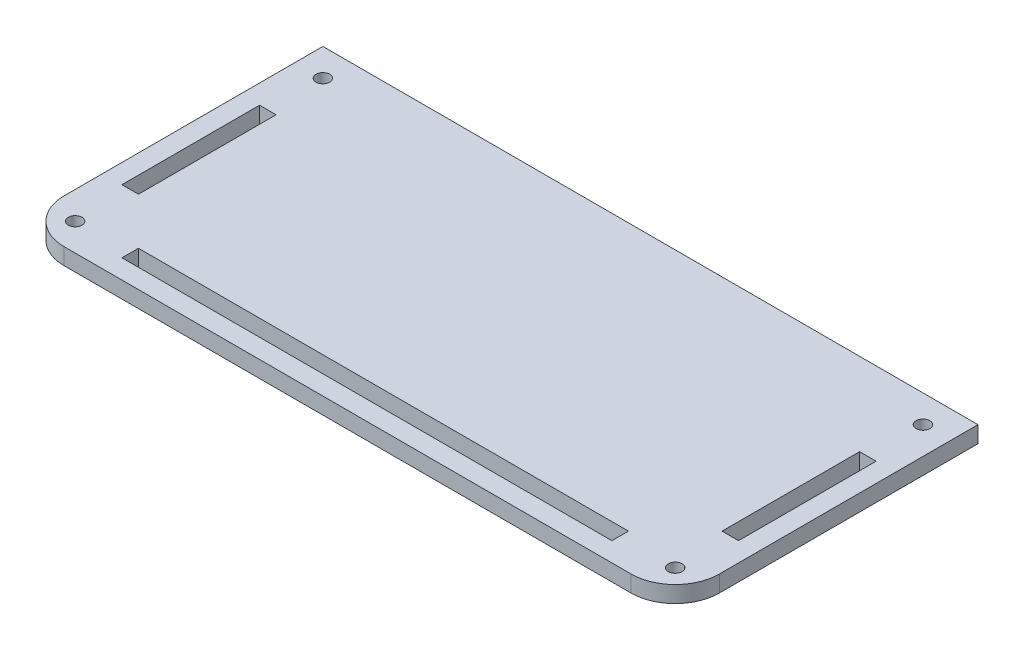
SolidWorks part; units mm, degrees
material "PVC rigido"
ref_plane "Piano frontale" through (0, 0, 0) normal (0, 0, 1) x (1, 0, 0)
ref_plane "Piano superiore" through (0, 0, 0) normal (0, 1, 0) x (1, 0, 0)
ref_plane "Piano destro" through (0, 0, 0) normal (1, 0, 0) x (0, 0, -1)
sketch "Schizzo1" plane through (0, 0, 0) normal (0, 1, 0) x (1, 0, 0)
  line L1 (-59.5, -27.5) -> (59.5, -27.5)
  line L2 (-59.5, -27.5) -> (-59.5, 27.5)
  line L3 (-59.5, 27.5) -> (59.5, 27.5)
  line L4 (59.5, -27.5) -> (59.5, 27.5)
  line L5 (-59.5, -27.5) -> (59.5, 27.5) construction
  line L6 (-59.5, 27.5) -> (59.5, -27.5) construction
  line L7 (67.5, 0) -> (59.5, 0) construction
  line L8 (67.5, -27.5) -> (67.5, 21.5) construction
  line L9 (-59.5, 0) -> (-67.5, 0) construction
  line L10 (-67.5, 21.5) -> (-67.5, -27.5) construction
  point P0 (0, 0)
  dimension "D1" = 8
  dimension "D2" = 55
extrude "Estrusione-Estrusione1" add sketch "Schizzo1" along normal blind 3
hole_wizard "Foro filettato M3x0.5-1" positions "Schizzo3" profile "Schizzo2" tap size "M3x0.5" standard "Ansi Metric" end condition through all
sketch "Schizzo3" plane through (0, 3, 0) normal (0, 1, 0) x (1, 0, 0)
  line L16 (54.5, -22.5) -> (54.5, 22.5)
  line L17 (54.5, 22.5) -> (-54.5, 22.5)
  line L18 (-54.5, 22.5) -> (-54.5, -22.5)
  line L19 (-54.5, -22.5) -> (54.5, -22.5)
  line L20 (54.5, -22.5) -> (54.5, 22.5) construction
  line L21 (54.5, 22.5) -> (-54.5, 22.5) construction
  line L22 (-54.5, 22.5) -> (-54.5, -22.5) construction
  line L23 (-54.5, -22.5) -> (54.5, -22.5) construction
  point P0 (-54.5, -22.5)
  point P2 (54.5, -22.5)
  point P4 (54.5, 22.5)
  point P6 (-54.5, 22.5)
  dimension "D1" = 5
sketch "Schizzo2" plane through (-54.5, 3, 22.5) normal (1, 0, 0) x (0, 0, 1)
  line L0 (0, 0) -> (0, 3)
  line L1 (0, 3) -> (1.25, 3)
  line L2 (1.25, 3) -> (1.25, 0)
  line L5 (1.25, 0) -> (0, 0)
  line L11 (0, -6.35) -> (0, 107.95) construction
  dimension "Thru Tap Drill Dia." = 2.5
  dimension "Thru Tap Drill Depth" = 3
cosmetic thread "Filettatura del foro1" parameters "D2"=3
cosmetic thread "Filettatura del foro2" parameters "D2"=3
cosmetic thread "Filettatura del foro3" parameters "D2"=3
cosmetic thread "Filettatura del foro4" parameters "D2"=3
sketch "Schizzo4" plane through (0, 3, 0) normal (0, 1, 0) x (1, 0, 0)
  line L0 (-54.5, -22.5) -> (-44.5, -22.5) construction
  line L1 (-44.5, -22.5) -> (44.5, -22.5) construction
  line L2 (44.5, -22.5) -> (54.5, -22.5) construction
  line L3 (54.5, -22.5) -> (54.5, -12.5) construction
  line L4 (54.5, -12.5) -> (54.5, 12.5) construction
  line L5 (54.5, 12.5) -> (54.5, 22.5) construction
  line L6 (-54.5, -22.5) -> (-54.5, -12.5) construction
  line L7 (-54.5, -12.5) -> (-54.5, 12.5) construction
  line L8 (-54.5, 12.5) -> (-54.5, 22.5) construction
  line L10 (-44.5, -24) -> (44.5, -24)
  line L11 (-44.5, -24) -> (-44.5, -21)
  line L12 (-44.5, -21) -> (44.5, -21)
  line L13 (44.5, -24) -> (44.5, -21)
  line L14 (53, 12.5) -> (56, 12.5)
  line L15 (53, 12.5) -> (53, -12.5)
  line L16 (53, -12.5) -> (56, -12.5)
  line L17 (56, 12.5) -> (56, -12.5)
  line L18 (-53, -12.5) -> (-56, -12.5)
  line L19 (-53, -12.5) -> (-53, 12.5)
  line L20 (-53, 12.5) -> (-56, 12.5)
  line L21 (-56, -12.5) -> (-56, 12.5)
  dimension "D1" = 10
  dimension "D2" = 3
extrude "Taglio-Estrusione1" cut sketch "Schizzo4" against normal through all
fillet "Raccordo1" radius 8 2 edges at (-59.5, 1.5, 27.5) (59.5, 1.5, 27.5)
